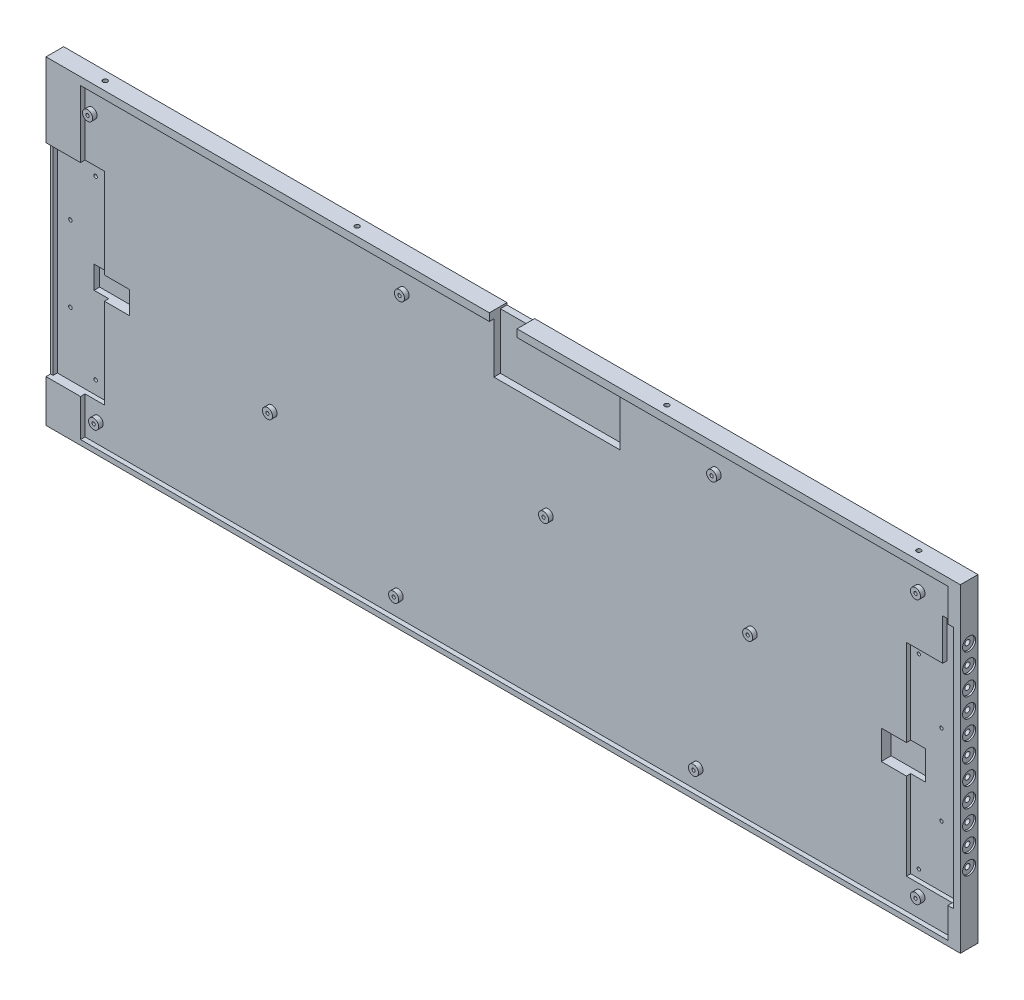
SolidWorks part; units mm, degrees
ref_plane "前视基准面" through (0, 0, 0) normal (0, 0, 1) x (1, 0, 0)
ref_plane "上视基准面" through (0, 0, 0) normal (0, 1, 0) x (1, 0, 0)
ref_plane "右视基准面" through (0, 0, 0) normal (1, 0, 0) x (0, 0, -1)
other "Configuration Table"
sketch "草图1" plane through (0, 0, 0) normal (0, 0, 1) x (1, 0, 0)
  line L1 (0, 0) -> (348.235, 0)
  line L2 (0, 0) -> (0, -124.71)
  line L3 (0, -124.71) -> (348.235, -124.71)
  line L4 (348.235, 0) -> (348.235, -124.71)
  dimension "D1" = 348.235
  dimension "D2" = 124.71
extrude "凸台-拉伸1" add sketch "草图1" along normal blind 7
sketch "草图2" plane through (0, 0, 7) normal (0, 0, 1) x (1, 0, 0)
  line L0 (348.235, 0) -> (0, 0) construction
  line L1 (2, -2) -> (346.235, -2)
  line L2 (2, -2) -> (2, -122.71)
  line L3 (2, -122.71) -> (346.235, -122.71)
  line L4 (346.235, -2) -> (346.235, -122.71)
  line L5 (348.235, -124.71) -> (348.235, 0) construction
  line L6 (0, -124.71) -> (348.235, -124.71) construction
  line L7 (0, 0) -> (0, -124.71) construction
  dimension "D1" = 2
  dimension "D2" = 2
  dimension "D3" = 2
  dimension "D4" = 2
extrude "切除-拉伸1" cut sketch "草图2" against normal blind 1.8
sketch "草图3" plane through (0, 0, 5.2) normal (0, 0, 1) x (1, 0, 0)
  circle A0 centre (4.8, -9.9) radius 2
  circle A1 centre (4.8, -9.9) radius 0.65
  circle A2 centre (7.2, -114.7) radius 2
  circle A3 centre (7.2, -114.7) radius 0.65
  circle A4 centre (76.2, -76.6) radius 2
  circle A5 centre (76.2, -76.6) radius 0.65
  circle A6 centre (128.6, -9.9) radius 2
  circle A7 centre (128.6, -9.9) radius 0.65
  circle A8 centre (126.3, -114.7) radius 2
  circle A9 centre (126.3, -114.7) radius 0.65
  circle A10 centre (185.8, -57.5) radius 2
  circle A11 centre (185.8, -57.5) radius 0.65
  circle A12 centre (252.5, -9.9) radius 2
  circle A13 centre (252.5, -9.9) radius 0.65
  circle A14 centre (245.3, -114.7) radius 2
  circle A15 centre (245.3, -114.7) radius 0.65
  circle A16 centre (333.4, -9.9) radius 2
  circle A17 centre (333.4, -9.9) radius 0.65
  circle A18 centre (333.4, -114.7) radius 2
  circle A19 centre (333.4, -114.7) radius 0.65
  circle A20 centre (266.8, -57.5) radius 2
  circle A21 centre (266.8, -57.5) radius 0.65
  dimension "D1" = 4
  dimension "D2" = 1.3
extrude "凸台-拉伸2" add sketch "草图3" along normal up to surface (1.8 mm away) up to face at (174.1175, -62.355, 7)
sketch "草图4" plane through (0, 0, 5.2) normal (0, 0, 1) x (1, 0, 0)
  line L0 (0, 0) -> (0, -124.71) construction
  line L1 (0, -27.51) -> (9.7, -27.51)
  line L2 (0, -27.51) -> (0, -107.91)
  line L3 (0, -107.91) -> (9.7, -107.91)
  line L4 (9.7, -27.51) -> (9.7, -107.91)
  line L5 (0, -124.71) -> (348.235, -124.71) construction
  dimension "D1" = 80.4
  dimension "D2" = 9.7
  dimension "D3" = 16.8
extrude "切除-拉伸2" cut sketch "草图4" against normal blind 1.7 and the other way through all contours L4 L3 L2 L1
sketch "草图6" plane through (0, 0, 5.2) normal (0, 0, 1) x (1, 0, 0)
  line L5 (3.9, -67.71) -> (9.7, -67.71) construction
  line L6 (3.9, -63.21) -> (19.7, -63.21)
  line L7 (3.9, -63.21) -> (3.9, -72.21)
  line L8 (3.9, -72.21) -> (19.7, -72.21)
  line L9 (19.7, -63.21) -> (19.7, -72.21)
  line L10 (9.7, -27.51) -> (9.7, -107.91) construction
  dimension "D1" = 9
  dimension "D2" = 5.8
  dimension "D3" = 10
extrude "切除-拉伸3" cut sketch "草图6" against normal offset from surface (3.9 mm away) 1.3 up to face at (174.1175, -62.355, 0)
sketch "草图7" plane through (0, 0, 0) normal (-1, 0, 0) x (0, 0, 1)
  line L1 (0, 0) -> (7, 0)
  line L2 (0, 0) -> (0, -27.51)
  line L3 (0, -27.51) -> (7, -27.51)
  line L4 (7, 0) -> (7, -27.51)
  line L5 (7, -107.91) -> (0, -107.91)
  line L6 (7, -107.91) -> (7, -124.71)
  line L7 (7, -124.71) -> (0, -124.71)
  line L8 (0, -107.91) -> (0, -124.71)
  line L9 (0, -107.91) -> (3.5, -107.91)
  line L10 (0, -107.91) -> (0, -27.51)
  line L11 (0, -27.51) -> (3.5, -27.51)
  line L12 (3.5, -107.91) -> (3.5, -27.51)
  line M1 (3.5, -107.91) -> (3.5, -27.51)
  line M2 (3.5, -27.51) -> (7, -27.51)
  line M3 (7, -27.51) -> (7, 0)
  line M4 (7, 0) -> (0, 0)
  line M5 (0, 0) -> (0, -124.71)
  line M6 (0, -124.71) -> (7, -124.71)
  line M7 (7, -124.71) -> (7, -107.91)
  line M8 (7, -107.91) -> (3.5, -107.91)
extrude "凸台-拉伸3" add sketch "草图7" along normal blind 11.7 contours L5 M8 M5 M6 M7 | L5 L3 M1 M5 | L3 M5 M2 M3 M4 region at (0, -13.755, 3.5) region at (0, -67.71, 1.75) region at (0, -116.31, 3.5)
sketch "草图8" plane through (0, 0, 3.5) normal (0, 0, 1) x (1, 0, 0)
  circle A0 centre (-5.5, -82.714) radius 0.7
  circle A1 centre (4.5, -102.714) radius 0.7
  circle A2 centre (-5.5, -52.714) radius 0.7
  circle A3 centre (4.5, -32.714) radius 0.7
  dimension "D1" = 1.4
extrude "切除-拉伸4" cut sketch "草图8" against normal blind 3
sketch "草图9" plane through (0, 0, 3.5) normal (0, 0, 1) x (1, 0, 0)
  line L0 (-11.7, -107.91) -> (2, -107.91) construction
  line L1 (-11.7, -27.51) -> (-10.7, -27.51)
  line L2 (-11.7, -27.51) -> (-11.7, -107.91)
  line L3 (-11.7, -107.91) -> (-10.7, -107.91)
  line L4 (-10.7, -27.51) -> (-10.7, -107.91)
  dimension "D1" = 1
extrude "凸台-拉伸4" add sketch "草图9" along normal up to surface (1.7 mm away) up to face at (64.8892, -65.925, 5.2)
sketch "草图10" plane through (0, 0, 5.2) normal (0, 0, 1) x (1, 0, 0)
  line L1 (328.035, -30.31) -> (348.235, -30.31)
  line L2 (328.035, -30.31) -> (328.035, -110.71)
  line L3 (328.035, -110.71) -> (348.235, -110.71)
  line L4 (348.235, -30.31) -> (348.235, -110.71)
  line L6 (348.235, -124.71) -> (348.235, 0) construction
  line L9 (2, -122.71) -> (346.235, -122.71) construction
  dimension "D1" = 80.4
  dimension "D2" = 20.2
  dimension "D3" = 12
extrude "切除-拉伸5" cut sketch "草图10" against normal blind 1.7 and the other way through all
sketch "草图11" plane through (0, 0, 3.5) normal (0, 0, 1) x (1, 0, 0)
  line L0 (328.035, -70.51) -> (333.835, -70.51) construction
  line L1 (318.035, -64.76) -> (333.835, -64.76)
  line L2 (318.035, -64.76) -> (318.035, -76.26)
  line L3 (318.035, -76.26) -> (333.835, -76.26)
  line L4 (333.835, -64.76) -> (333.835, -76.26)
  line L5 (328.035, -110.71) -> (328.035, -30.31) construction
  dimension "D1" = 11.5
  dimension "D2" = 5.8
  dimension "D3" = 10
extrude "切除-拉伸6" cut sketch "草图11" against normal blind 2.2 and the other way through all
sketch "草图12" plane through (0, 0, 3.5) normal (0, 0, 1) x (1, 0, 0)
  circle A3 centre (331.235, -107.514) radius 0.65
  circle A4 centre (340.235, -86.514) radius 0.65
  circle A5 centre (340.235, -54.514) radius 0.65
  circle A6 centre (331.235, -33.514) radius 0.65
  dimension "D1" = 1.3
extrude "切除-拉伸7" cut sketch "草图12" against normal blind 3
sketch "草图13" plane through (0, 0, 0) normal (0, 0, -1) x (-1, 0, 0)
  line L0 (11.7, -124.71) -> (-348.235, -124.71) construction
  line L1 (-348.235, 0) -> (-351.235, 0)
  line L2 (-348.235, 0) -> (-348.235, -124.71)
  line L3 (-348.235, -124.71) -> (-351.235, -124.71)
  line L4 (-351.235, 0) -> (-351.235, -124.71)
  dimension "D1" = 3
extrude "凸台-拉伸5" add sketch "草图13" against normal up to surface (7 mm away) up to face at (171.1925, -14.955, 7)
sketch "草图14" plane through (0, 0, 5.2) normal (0, 0, 1) x (1, 0, 0)
  line L0 (346.235, -2) -> (2, -2) construction
  line L1 (342.435, -14) -> (348.435, -14)
  line L2 (342.435, -14) -> (342.435, -110.71)
  line L3 (342.435, -110.71) -> (348.435, -110.71)
  line L4 (348.435, -14) -> (348.435, -110.71)
  line L5 (346.235, -110.71) -> (328.035, -110.71) construction
  line L6 (351.235, 0) -> (351.235, -124.71) construction
  dimension "D1" = 12
  dimension "D2" = 6
  dimension "D3" = 2.8
extrude "切除-拉伸8" cut sketch "草图14" against normal up to surface (1.7 mm away) and the other way blind 3 up to face at (340.885, -86.514, 3.5)
sketch "草图15" plane through (351.235, 0, 0) normal (1, 0, 0) x (0, 0, -1)
  line L0 (-7, 0) -> (0, 0) construction
  line L1 (-3.5, -20) -> (-3.5, 0)
  line L2 (-3.5, -104.71) -> (-3.5, -124.71)
  line L4 (-7, -124.71) -> (0, -124.71) construction
  circle A0 centre (-3.5, -20) radius 2.6
  circle A12 centre (-3.5, -20) radius 1
  circle A13 centre (-3.5, -27.7009) radius 2.6
  circle A14 centre (-3.5, -27.7009) radius 1
  circle A15 centre (-3.5, -35.4018) radius 2.6
  circle A16 centre (-3.5, -35.4018) radius 1
  circle A17 centre (-3.5, -43.1027) radius 2.6
  circle A18 centre (-3.5, -43.1027) radius 1
  circle A19 centre (-3.5, -50.8036) radius 2.6
  circle A20 centre (-3.5, -50.8036) radius 1
  circle A21 centre (-3.5, -58.5045) radius 2.6
  circle A22 centre (-3.5, -58.5045) radius 1
  circle A23 centre (-3.5, -66.2055) radius 2.6
  circle A24 centre (-3.5, -66.2055) radius 1
  circle A25 centre (-3.5, -73.9064) radius 2.6
  circle A26 centre (-3.5, -73.9064) radius 1
  circle A27 centre (-3.5, -81.6073) radius 2.6
  circle A28 centre (-3.5, -81.6073) radius 1
  circle A29 centre (-3.5, -89.3082) radius 2.6
  circle A30 centre (-3.5, -89.3082) radius 1
  circle A31 centre (-3.5, -97.0091) radius 2.6
  circle A32 centre (-3.5, -97.0091) radius 1
  circle A33 centre (-3.5, -104.71) radius 2.6
  circle A34 centre (-3.5, -104.71) radius 1
  point P5 (-3.5, 0)
  dimension "D2" = 5.2
  dimension "D3" = 2
  dimension "D1" = 20
  dimension "D4" = 12
extrude "切除-拉伸9" cut sketch "草图15" against normal blind 0.7 contours A0 | A13 | A15 | A17 | A19 | A21 | A23 | A25 | A27 | A29 | A31
extrude "切除-拉伸10" cut sketch "草图15<3>" against normal up to surface (2.8 mm away) contours A12 | A14 | A16 | A18 | A20 | A22 | A24 | A26 | A28 | A30 | A32 up to face at (348.435, -62.355, 5.25)
sketch "草图15<3>" plane through (351.235, 0, 0) normal (1, 0, 0) x (0, 0, -1) same geometry as "草图15"
sketch "草图16" plane through (0, 0, 0) normal (0, 1, 0) x (1, 0, 0)
  line L1 (-11.7, 0) -> (351.235, 0)
  line L2 (-11.7, 0) -> (-11.7, -7)
  line L3 (-11.7, -7) -> (351.235, -7)
  line L4 (351.235, 0) -> (351.235, -7)
extrude "凸台-拉伸6" add sketch "草图16" along normal blind 0.2
sketch "草图17" plane through (0, -124.71, 0) normal (0, -1, 0) x (1, 0, 0)
  line L1 (-11.7, 7) -> (351.235, 7)
  line L2 (-11.7, 7) -> (-11.7, 0)
  line L3 (-11.7, 0) -> (351.235, 0)
  line L4 (351.235, 7) -> (351.235, 0)
extrude "凸台-拉伸7" add sketch "草图17" along normal blind 0.2
sketch "草图23" plane through (0, 0, 0) normal (0, 0, -1) x (-1, 0, 0)
  line L0 (-351.235, 0.2) -> (-351.235, -124.91) construction
  line L1 (11.7, 0.2) -> (11.7, -124.91) construction
  line L2 (-351.235, 0.2) -> (11.7, 0.2) construction
  line L3 (11.7, -124.91) -> (-351.235, -124.91) construction
  circle A0 centre (-331.235, -19.8) radius 5.6
  circle A1 centre (-231.235, -19.8) radius 5.6
  circle A2 centre (-108.3, -19.8) radius 5.6
  circle A3 centre (-8.3, -19.8) radius 5.6
  circle A4 centre (-331.235, -104.91) radius 4.1
  circle A5 centre (-231.235, -104.91) radius 4.1
  circle A6 centre (-108.3, -104.91) radius 4.1
  circle A7 centre (-8.3, -104.91) radius 4.1
  dimension "D1" = 11.2
  dimension "D2" = 8.2
  dimension "D3" = 20
  dimension "D4" = 20
  dimension "D5" = 20
  dimension "D6" = 100
  dimension "D7" = 100
  dimension "D8" = 20
extrude "切除-拉伸14" cut sketch "草图23" against normal blind 1
sketch "草图24" plane through (0, 0.2, 0) normal (0, 1, 0) x (1, 0, 0)
  circle A0 centre (8.3, -3.5) radius 0.9
  circle A1 centre (108.3, -3.5) radius 0.9
  circle A2 centre (231.235, -3.5) radius 0.9
  circle A3 centre (331.235, -3.5) radius 0.9
  dimension "D1" = 1.8
sketch "草图25" plane through (0, 0.2, 0) normal (0, 1, 0) x (1, 0, 0)
  line L1 (-11.7, 0) -> (351.235, 0)
  line L2 (-11.7, 0) -> (-11.7, -7)
  line L3 (-11.7, -7) -> (351.235, -7)
  line L4 (351.235, 0) -> (351.235, -7)
extrude "凸台-拉伸8" add sketch "草图25" along normal blind 1.8
sketch "草图26" plane through (0, 0, 7) normal (0, 0, 1) x (1, 0, 0)
  line L0 (346.235, -14) -> (346.235, -2) construction
  line L1 (2, -2) -> (346.235, -2)
  line L2 (2, -2) -> (2, -1)
  line L3 (2, -1) -> (346.235, -1)
  line L4 (346.235, -2) -> (346.235, -1)
  dimension "D1" = 1
extrude "切除-拉伸15" cut sketch "草图26" against normal up to surface (1.8 mm away) up to face at (268.8, -57.5, 5.2)
sketch "草图27" plane through (0, 2, 0) normal (0, 1, 0) x (1, 0, 0)
  line L0 (351.235, 0) -> (-11.7, 0) construction
  line L1 (164.2675, 0) -> (175.2675, 0)
  line L2 (164.2675, 0) -> (164.2675, -7)
  line L3 (164.2675, -7) -> (175.2675, -7)
  line L4 (175.2675, 0) -> (175.2675, -7)
  line L5 (-11.7, -7) -> (351.235, -7) construction
  line L6 (164.2675, -4) -> (169.7675, -4) construction
  line L7 (169.7675, -4) -> (175.2675, -4) construction
  point P8 (169.7675, -4)
  dimension "D1" = 11
extrude "切除-拉伸16" cut sketch "草图27" against normal blind 0.8
sketch "草图28" plane through (0, 0, 5.2) normal (0, 0, 1) x (1, 0, 0)
  line L0 (346.235, -1) -> (2, -1) construction
  line L1 (164.2675, -1) -> (214.2675, -1)
  line L2 (164.2675, -1) -> (164.2675, -21)
  line L3 (164.2675, -21) -> (214.2675, -21)
  line L4 (214.2675, -1) -> (214.2675, -21)
  line L5 (164.2675, -1) -> (175.2675, -1)
  line L6 (164.2675, -1) -> (164.2675, 1.2)
  line L7 (164.2675, 1.2) -> (175.2675, 1.2)
  line L8 (175.2675, -1) -> (175.2675, 1.2)
  line L9 (164.2675, 1.2) -> (164.2675, 2) construction
  line M21 (346.235, -1) -> (2, -1)
  dimension "D1" = 20
  dimension "D2" = 50
extrude "切除-拉伸17" cut sketch "草图28" against normal blind 2.6 and the other way through all contours L4 L1 L2 L3 M21 | L1 L8 L7 L6 region at (169.7675, 0.1, 5.2) region at (189.2675, -11, 5.2)
sketch "草图29" plane through (-11.7, 0, 0) normal (-1, 0, 0) x (0, 0, 1)
  line L0 (0, 2) -> (0, -124.91) construction
  line L1 (7, -124.91) -> (0, -124.91)
  line L2 (7, -124.91) -> (7, -124.71)
  line L3 (7, -124.71) -> (0, -124.71)
  line L4 (0, -124.91) -> (0, -124.71)
  dimension "D1" = 0.2
extrude "切除-拉伸18" cut sketch "草图29" against normal through all
extrude "切除-拉伸19" cut sketch "草图24" against normal blind 2 from surface starting at face at (76.2837, 2, 3.5)
extrude "切除-拉伸20" cut sketch "草图24<3>" along normal blind 2 from surface starting at face at (169.7675, -124.71, 3.5)
sketch "草图24<3>" plane through (0, 0.2, 0) normal (0, 1, 0) x (1, 0, 0) same geometry as "草图24"
sketch "草图30" plane through (0, 0, 0) normal (0, 0, 1) x (1, 0, 0)
  line L1 (-87.4146, 53.5298) -> (160, 53.5298)
  line L2 (-87.4146, 53.5298) -> (-87.4146, -151.3065)
  line L3 (-87.4146, -151.3065) -> (160, -151.3065)
  line L4 (160, 53.5298) -> (160, -151.3065)
  dimension "D1" = 160
